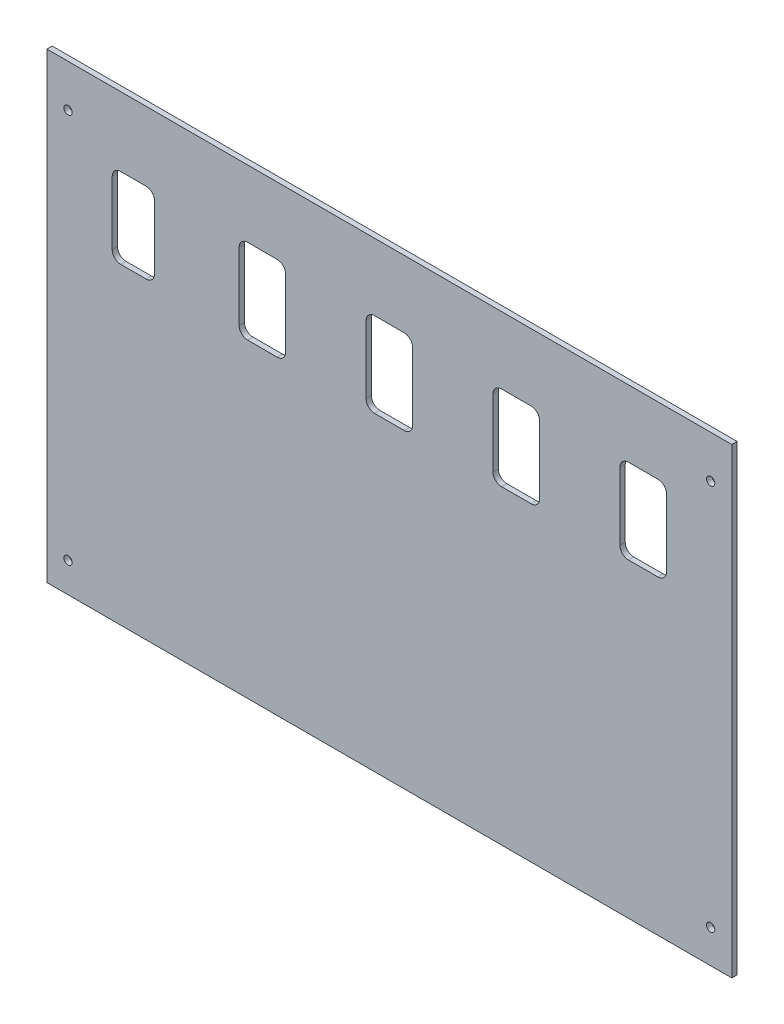
SolidWorks part; units mm, degrees
material "ABS PC"
ref_plane "Front Plane" through (0, 0, 0) normal (0, 0, 1) x (1, 0, 0)
ref_plane "Top Plane" through (0, 0, 0) normal (0, 1, 0) x (1, 0, 0)
ref_plane "Right Plane" through (0, 0, 0) normal (1, 0, 0) x (0, 0, -1)
sketch "Sketch1" plane through (0, 0, 0) normal (0, 0, 1) x (1, 0, 0)
  line L1 (-205.5812, -138.684) -> (205.5812, -138.684)
  line L2 (-205.5812, -138.684) -> (-205.5812, 138.684)
  line L3 (-205.5812, 138.684) -> (205.5812, 138.684)
  line L4 (205.5812, -138.684) -> (205.5812, 138.684)
  line L5 (0, 138.684) -> (0, -138.684) construction
  line L6 (-205.5812, 0) -> (205.5813, 0) construction
  point P0 (0, 0)
  point P4 (-137.0013, 0)
  point P5 (137.0013, 0)
  point P6 (0, 97.0788)
  point P7 (0, -97.0788)
  dimension "Width" = 277.368
  dimension "Break" = 68.58
  dimension "D2" = 68.58
  dimension "D1" = 41.6052
  dimension "D3" = 41.6052
  dimension "D4" = 411.1625
sketch "Sketch2" plane through (0, 0, 0) normal (1, 0, 0) x (0, 0, -1)
  line L0 (-1.5875, -138.684) -> (1.5875, -138.684)
  dimension "Thickness" = 3.175
sketch "Sketch3" plane through (0, 0, 0) normal (0, 0, 1) x (1, 0, 0)
  line L0 (-205.5812, -138.684) -> (-205.5812, 138.684) construction
  line L1 (-205.5812, -138.684) -> (205.5812, -138.684) construction
  line L2 (205.5812, -138.684) -> (205.5812, 138.684) construction
  line L3 (-205.5812, 138.684) -> (205.5812, 138.684) construction
  line L4 (-205.5812, -138.684) -> (-205.5812, 138.684)
  line L5 (-205.5812, -138.684) -> (205.5812, -138.684)
  line L6 (205.5812, -138.684) -> (205.5812, 138.684)
  line L7 (-205.5812, 138.684) -> (205.5812, 138.684)
extrude "Boss-Extrude1" add sketch "Sketch3" along normal mid plane 3.175
sketch "Sketch4" plane through (0, 0, 1.5875) normal (0, 0, 1) x (1, 0, 0)
  line L0 (-227.6475, 73.0327) -> (-161.29, 73.0327) construction
  line L1 (-82.55, 73.0327) -> (-82.55, 98.4327) construction
  line L2 (-82.55, 98.4327) -> (-90.17, 98.4327) construction
  line L3 (-161.29, 73.0327) -> (-161.29, 97.1627) construction
  line L6 (-227.6475, -105.791) -> (-227.6475, 52.959) construction
  line L7 (-227.6475, -115.316) -> (-227.6475, 138.684) construction
  line L8 (-161.29, 73.0327) -> (-82.55, 73.0327) construction
  line L9 (-82.55, 73.0327) -> (-6.35, 73.0327) construction
  line L10 (-6.35, 73.0327) -> (69.85, 73.0327) construction
  line L11 (69.85, 73.0327) -> (146.05, 73.0327) construction
  line L12 (-82.55, 73.0327) -> (-82.55, 47.6327) construction
  line L13 (-82.55, 47.6327) -> (-62.23, 47.6327) construction
  line L16 (-161.29, 97.1627) -> (-166.37, 97.1627) construction
  line L17 (-161.29, 73.0327) -> (-161.29, 48.9027) construction
  line L18 (-161.29, 48.9027) -> (-140.97, 48.9027) construction
  line L19 (-6.35, 73.0327) -> (-6.35, 98.4327) construction
  line L24 (-6.35, 98.4327) -> (-13.97, 98.4327) construction
  line L25 (-6.35, 73.0327) -> (-6.35, 47.6327) construction
  line L26 (-6.35, 47.6327) -> (13.97, 47.6327) construction
  line L27 (69.85, 73.0327) -> (69.85, 98.4327) construction
  line L28 (-8.89, 98.4327) -> (8.89, 98.4327)
  line L29 (-13.97, 93.3527) -> (-13.97, 52.7127)
  line L30 (-8.89, 47.6327) -> (8.89, 47.6327)
  line L31 (13.97, 93.3527) -> (13.97, 52.7127)
  line L32 (69.85, 98.4327) -> (62.23, 98.4327) construction
  line L33 (69.85, 73.0327) -> (69.85, 47.6327) construction
  line L34 (69.85, 47.6327) -> (90.17, 47.6327) construction
  line L35 (146.05, 73.0327) -> (146.05, 98.4327) construction
  line L36 (67.31, 98.4327) -> (85.09, 98.4327)
  line L37 (62.23, 93.3527) -> (62.23, 52.7127)
  line L38 (67.31, 47.6327) -> (85.09, 47.6327)
  line L39 (90.17, 93.3527) -> (90.17, 52.7127)
  line L40 (146.05, 98.4327) -> (138.43, 98.4327) construction
  line L41 (146.05, 73.0327) -> (146.05, 47.6327) construction
  line L42 (146.05, 47.6327) -> (166.37, 47.6327) construction
  line L43 (-205.5812, 138.684) -> (-205.5812, 73.0327) construction
  line L44 (143.51, 98.4327) -> (161.29, 98.4327)
  line L45 (138.43, 93.3527) -> (138.43, 52.7127)
  line L46 (143.51, 47.6327) -> (161.29, 47.6327)
  line L47 (166.37, 93.3527) -> (166.37, 52.7127)
  line L48 (-85.09, 98.4327) -> (-67.31, 98.4327)
  line L49 (-90.17, 93.3527) -> (-90.17, 52.7127)
  line L50 (-85.09, 47.6327) -> (-67.31, 47.6327)
  line L51 (-62.23, 93.3527) -> (-62.23, 52.7127)
  line L53 (-161.29, 97.1627) -> (-146.05, 97.1627)
  line L54 (-166.37, 92.0827) -> (-166.37, 53.9827)
  line L55 (-161.29, 48.9027) -> (-146.05, 48.9027)
  line L56 (-140.97, 92.0827) -> (-140.97, 53.9827)
  arc A0 (138.43, 52.7127) -> (143.51, 47.6327) centre (143.51, 52.7127) ccw
  arc A1 (166.37, 52.7127) -> (161.29, 47.6327) centre (161.29, 52.7127) cw
  arc A2 (161.29, 98.4327) -> (166.37, 93.3527) centre (161.29, 93.3527) cw
  arc A3 (138.43, 93.3527) -> (143.51, 98.4327) centre (143.51, 93.3527) cw
  arc A4 (62.23, 52.7127) -> (67.31, 47.6327) centre (67.31, 52.7127) ccw
  arc A5 (90.17, 52.7127) -> (85.09, 47.6327) centre (85.09, 52.7127) cw
  arc A6 (85.09, 98.4327) -> (90.17, 93.3527) centre (85.09, 93.3527) cw
  arc A7 (67.31, 98.4327) -> (62.23, 93.3527) centre (67.31, 93.3527) ccw
  arc A8 (-13.97, 52.7127) -> (-8.89, 47.6327) centre (-8.89, 52.7127) ccw
  arc A9 (13.97, 52.7127) -> (8.89, 47.6327) centre (8.89, 52.7127) cw
  arc A10 (8.89, 98.4327) -> (13.97, 93.3527) centre (8.89, 93.3527) cw
  arc A11 (-8.89, 98.4327) -> (-13.97, 93.3527) centre (-8.89, 93.3527) ccw
  arc A19 (-90.17, 52.7127) -> (-85.09, 47.6327) centre (-85.09, 52.7127) ccw
  arc A20 (-62.23, 52.7127) -> (-67.31, 47.6327) centre (-67.31, 52.7127) cw
  arc A21 (-67.31, 98.4327) -> (-62.23, 93.3527) centre (-67.31, 93.3527) cw
  arc A22 (-85.09, 98.4327) -> (-90.17, 93.3527) centre (-85.09, 93.3527) ccw
  arc A23 (-166.37, 53.9827) -> (-161.29, 48.9027) centre (-161.29, 53.9827) ccw
  arc A24 (-146.05, 48.9027) -> (-140.97, 53.9827) centre (-146.05, 53.9827) ccw
  arc A25 (-146.05, 97.1627) -> (-140.97, 92.0827) centre (-146.05, 92.0827) cw
  arc A26 (-161.29, 97.1627) -> (-166.37, 92.0827) centre (-161.29, 92.0827) ccw
  point P16 (-76.2, 98.4327)
  point P17 (-90.17, 73.0327)
  point P18 (-13.97, 73.0327)
  point P95 (62.23, 73.0327)
  point P96 (138.43, 73.0327)
  point P97 (0, 98.4327)
  point P98 (76.2, 98.4327)
  point P99 (152.4, 98.4327)
  dimension "D1" = 5.08
  dimension "D2" = 5.08
  dimension "D5" = 5.08
  dimension "D9" = 27.94
  dimension "D10" = 27.94
  dimension "D11" = 27.94
  dimension "D12" = 27.94
  dimension "D3" = 76.2
  dimension "D4" = 76.2
  dimension "D6" = 152.4
  dimension "D7" = 65.6513
extrude "Cut-Extrude1" cut sketch "Sketch4" against normal blind 25.4 contours L53 A26 L54 A23 L55 A24 L56 A25 | A22 L48 A21 L51 A20 L50 A19 L49 | L29 A8 L30 A9 L31 A10 L28 A11 | L37 A4 L38 A5 L39 A6 L36 A7 | A3 L44 A2 L47 A1 L46 A0 L45 region at (-153.67, 73.0327, 1.5875)
hole_wizard "#10 Clearance Hole1" positions "Sketch5" profile "Sketch6" hole size "#10" standard "ANSI Inch" end condition through all
sketch "Sketch5" plane through (0, 0, 1.5875) normal (0, 0, 1) x (1, 0, 0)
  point P6 (192.8812, 113.284)
  point P8 (-192.8812, -120.7642)
  point P10 (192.8812, -118.6475)
  point P12 (-192.8812, 113.284)
sketch "Sketch6" plane through (192.8812, 113.284, 1.5875) normal (1, 0, 0) x (0, -1, 0)
  line L0 (0, 0) -> (0, 3.175)
  line L1 (0, 3.175) -> (2.4892, 3.175)
  line L2 (2.4892, 3.175) -> (2.4892, 0)
  line L5 (2.4892, 0) -> (0, 0)
  line L11 (0, -6.35) -> (0, 107.95) construction
  dimension "Thru Hole Dia." = 4.9784
  dimension "Thru Hole Depth" = 3.175
equation "\"D1@Boss-Extrude1\" = \"Thickness@Sketch2\""
equation "\"D2@Sketch1\" = \"Break@Sketch1\""
equation "\"D1@Sketch1\"=\"Width@Sketch1\"*0.15"
equation "\"D3@Sketch1\"=\"D1@Sketch1\""
equation "\"SlotWidth\"= 1.1in"
equation "\"D9@Sketch4\"=\"SlotWidth\""
equation "\"D10@Sketch4\"=\"SlotWidth\""
equation "\"D11@Sketch4\"=\"SlotWidth\""
equation "\"D12@Sketch4\"=\"SlotWidth\""
